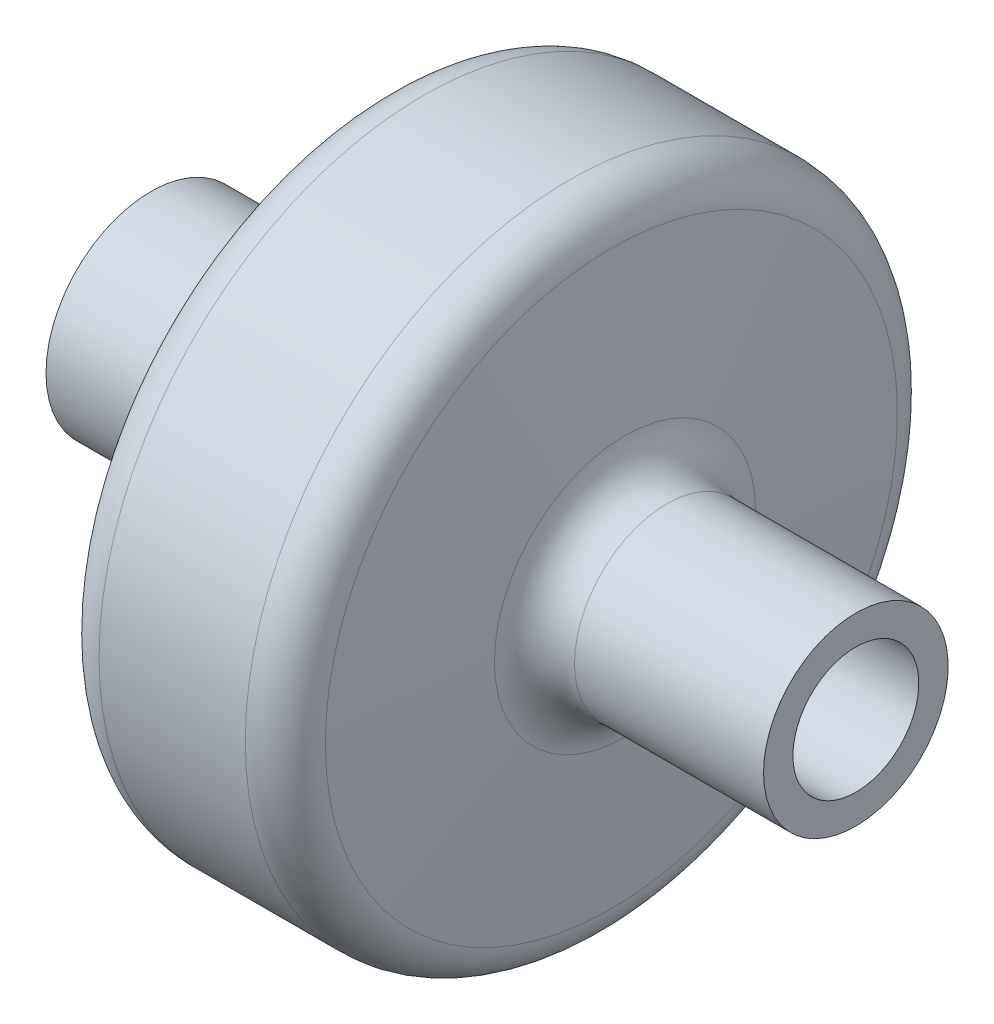
SolidWorks part; units mm, degrees
ref_plane "Front" through (0, 0, 0) normal (0, 0, 1) x (1, 0, 0)
ref_plane "Top" through (0, 0, 0) normal (0, 1, 0) x (1, 0, 0)
ref_plane "Right" through (0, 0, 0) normal (1, 0, 0) x (0, 0, -1)
ref_axis "Axis1" through (0, 0, 55) along (0, 0, -1)
sketch "Sketch1" plane through (0, 0, 0) normal (0, 0, 1) x (1, 0, 0)
  line L0 (-39.9221, 0) -> (39.9221, 0) construction
  line L3 (-6.5329, 36.65) -> (6.5329, 36.65)
  line L4 (11.5329, 31.65) -> (11.5329, 7.5)
  line L5 (11.5329, 7.5) -> (43.0582, 7.5)
  line L6 (43.0582, 7.5) -> (43.0582, 11)
  line L7 (43.0582, 11) -> (20.5336, 11)
  line L8 (13.5329, 11) -> (13.5329, 38.65) construction
  line L9 (8.9512, 38.65) -> (-8.4718, 38.65)
  line L10 (-13.0535, 38.65) -> (-13.0535, 11) construction
  line L12 (-40.9418, 12.5) -> (-40.9418, 11)
  line L13 (0, 0) -> (0, 36.65) construction
  line L14 (-13.4528, 34.0858) -> (-15.0732, 15.5642)
  line L15 (13.9322, 34.0858) -> (15.5526, 15.5642)
  line L16 (-11.5329, 11) -> (15.9519, 11) construction
  line L17 (-18.4172, 12.5) -> (-40.9418, 12.5)
  line L18 (-40.9418, 11) -> (-20.9903, 11)
  line L19 (-11.5329, 31.65) -> (-11.5329, 11)
  line L20 (-11.5329, 11) -> (-20.9903, 11)
  arc A0 (-6.5329, 36.65) -> (-11.5329, 31.65) centre (-6.5329, 31.65) ccw
  arc A1 (11.5329, 31.65) -> (6.5329, 36.65) centre (6.5329, 31.65) ccw
  arc A2 (13.9322, 34.0858) -> (8.9512, 38.65) centre (8.9512, 33.65) ccw
  arc A3 (-13.4528, 34.0858) -> (-8.4718, 38.65) centre (-8.4718, 33.65) cw
  arc A4 (20.5336, 11) -> (15.5526, 15.5642) centre (20.5336, 16) cw
  arc A5 (-18.4172, 12.5) -> (-15.0732, 15.5642) centre (-18.4172, 15.8568) ccw
  point P4 (0, 0)
  point P6 (0, 0)
  point P19 (13.5329, 24.825)
  point P21 (0, 0)
  point P39 (-11.843, 11)
  point P40 (0, 0)
  point P41 (-6.5329, 36.65)
  dimension "D10" = 5
  dimension "D11" = 5
  dimension "D14" = 3.3568
  dimension "D2" = 22
  dimension "D3" = 15
  dimension "D4" = 22
  dimension "D5" = 2
  dimension "D6" = 2
  dimension "D7" = 77.3
  dimension "D8" = 25.0658
  dimension "D9" = 27.385
  dimension "D12" = 4.0197
  dimension "D13" = 25
  dimension "D15" = 84
revolve "Revolve1" add sketch "Sketch1" angle 360 about L0
